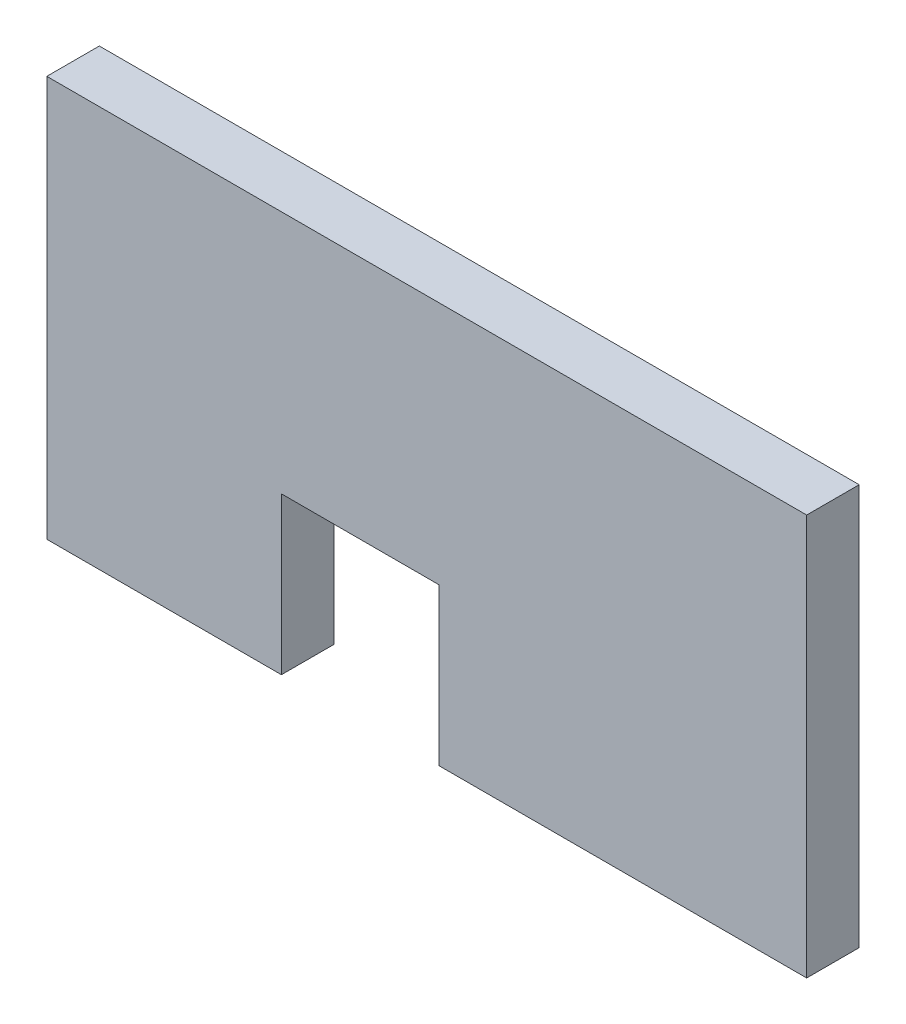
SolidWorks part; units mm, degrees
ref_plane "Front Plane" through (0, 0, 0) normal (0, 0, 1) x (1, 0, 0)
ref_plane "Top Plane" through (0, 0, 0) normal (0, 1, 0) x (1, 0, 0)
ref_plane "Right Plane" through (0, 0, 0) normal (1, 0, 0) x (0, 0, -1)
sketch "Sketch1" plane through (0, 0, 0) normal (0, 0, 1) x (1, 0, 0)
  line L0 (21.7, 33.35) -> (21.7, 15.05) construction
  line L1 (21.7, 37.95) -> (-21.7, 37.95)
  line L2 (21.7, 37.95) -> (21.7, 15.05)
  line L3 (21.7, 15.05) -> (0.7, 15.05)
  line L4 (-21.7, 37.95) -> (-21.7, 15.05)
  line L5 (-21.7, 33.35) -> (-21.7, 15.05) construction
  line L6 (32.157, 37.95) -> (-32.157, 37.95) construction
  line L7 (28.7, 15.05) -> (-28.7, 15.05) construction
  line L8 (0.7, 15.05) -> (0.7, 24) construction
  line L9 (0.7, 24) -> (-8.3, 24) construction
  line L10 (-8.3, 24) -> (-8.3, 15.05) construction
  line L11 (0.7, 15.05) -> (0.7, 24)
  line L12 (0.7, 24) -> (-8.3, 24)
  line L13 (-8.3, 24) -> (-8.3, 15.05)
  line L14 (-8.3, 15.05) -> (-21.7, 15.05)
sketch "Sketch2" plane through (0, 0, 0) normal (1, 0, 0) x (0, 0, -1)
  line L0 (0, 19.65) -> (0, 37.95) construction
  line L1 (0, 37.95) -> (-3, 37.95)
  line L2 (0, 37.95) -> (0, 15.05)
  line L3 (0, 15.05) -> (-3, 15.05)
  line L4 (-3, 37.95) -> (-3, 15.05)
  line L5 (-3, 19.65) -> (-3, 34.95) construction
  line L6 (-53.857, 15.05) -> (10.457, 15.05) construction
  line L7 (-50.4, 37.95) -> (7, 37.95) construction
extrude "Boss-Extrude1" add sketch "Sketch1" along normal up to vertex (3 mm away) up to point (0, 37.95, 3)
